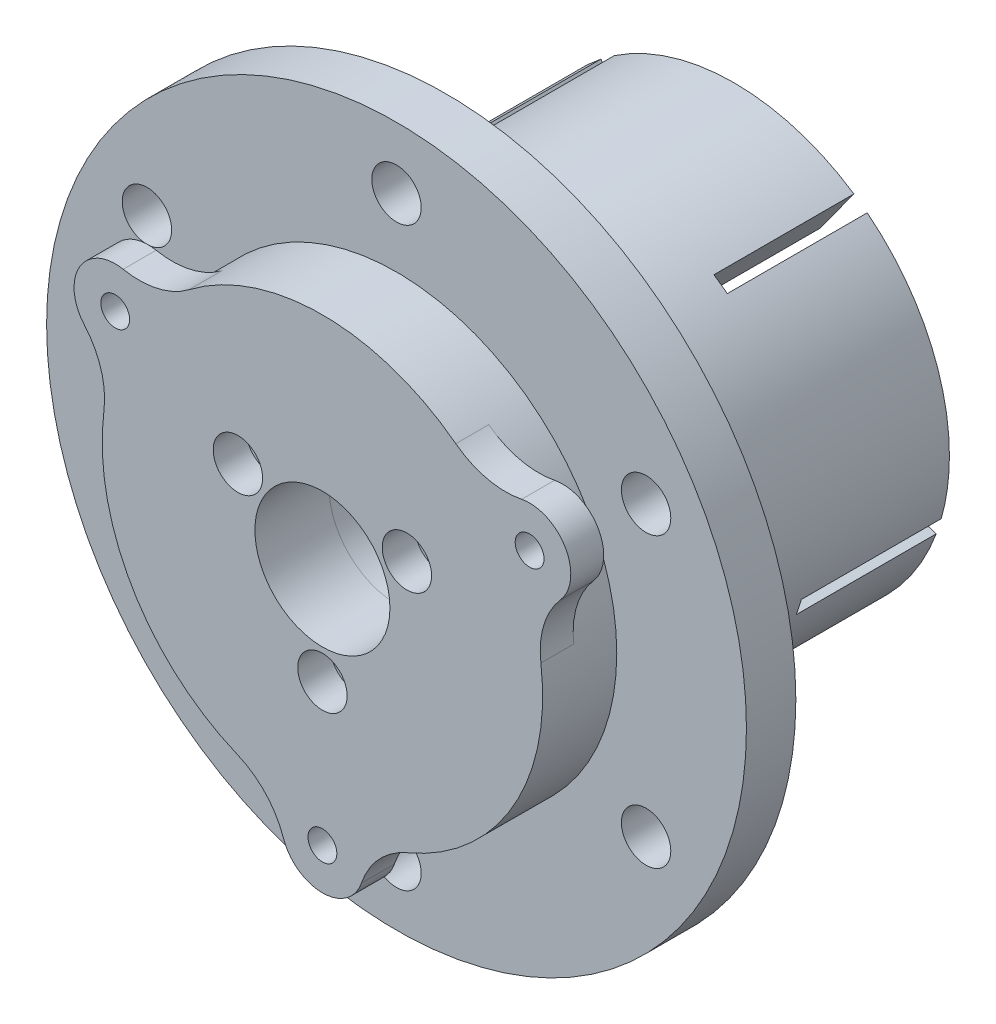
SolidWorks part; units mm, degrees
other "PCB Fixture"
other "Fanatec adapter V2"
ref_plane "Front Plane" through (0, 0, 0) normal (0, 0, 1) x (1, 0, 0)
ref_plane "Top Plane" through (0, 0, 0) normal (0, 1, 0) x (1, 0, 0)
ref_plane "Right Plane" through (0, 0, 0) normal (1, 0, 0) x (0, 0, -1)
sketch "Sketch1" plane through (0, 0, 0) normal (0, 0, 1) x (1, 0, 0)
  line L1 (-2.9, 18.9291) -> (2.9, 18.9291) construction
  line L2 (-2.9, 18.9291) -> (-2.9, 16.7508)
  line L4 (2.9, 18.9291) -> (2.9, 16.7508)
  circle A0 centre (0, 0) radius 19.15
  circle A1 centre (0, 0) radius 17
  circle A2 centre (0, 0) radius 26.15
  point P7 (0, 17)
  point P13 (0, 18.9291)
  dimension "D1" = 38.3
  dimension "D3" = 34
  dimension "D4" = 7
  dimension "D2" = 5.8
extrude "Boss-Extrude1" add sketch "Sketch1" against normal blind 35 contours A2 A0 | L1 L2 A1 L4 | A0 L1 region at (0, 19.0175, 0) region at (0, 17.9218, 0) region at (-25.4104, 0, 0)
fillet "Fillet1" radius 0.7 2 edges at (2.9, 18.9291, -17.5) (-2.9, 18.9291, -17.5)
sketch "Sketch2" plane through (0, 0, 0) normal (0, 0, 1) x (1, 0, 0)
  line L0 (0, -8.2) -> (0, -15.5) construction
  circle A0 centre (0, 35) radius 3
  circle A1 centre (30.3109, 17.5) radius 3
  circle A2 centre (30.3109, -17.5) radius 3
  circle A3 centre (0, -35) radius 3
  circle A4 centre (-30.3109, -17.5) radius 3
  circle A5 centre (-30.3109, 17.5) radius 3
  circle A6 centre (0, 0) radius 42.5
  circle A7 centre (0, 0) radius 8.2
  circle A8 centre (0, 0) radius 17 construction
  circle A10 centre (0, 0) radius 17
  circle A11 centre (0, -11.85) radius 1.35
  circle A13 centre (-10.2624, 5.925) radius 1.35
  circle A14 centre (10.2624, 5.925) radius 1.35
  point P15 (0, 0)
  point P34 (0, 0)
  dimension "D2" = 6
  dimension "D4" = 85
  dimension "D5" = 16.4
  dimension "D6" = 2.7
  dimension "D1" = 35
  dimension "D9" = 15.5
  dimension "D3" = 6
  dimension "D7" = 3
extrude "Boss-Extrude2" add sketch "Sketch2" along normal blind 6 contours A6 A10 A0 A1 A2 A3 A4 A5 | A10 A7 region at (-41.2979, 0, 0) region at (-16.5192, 0, 0)
sketch "Sketch3" plane through (0, 0, -35) normal (0, 0, -1) x (-1, 0, 0)
  line L1 (-1, -27.5229) -> (1, -27.5229)
  line L2 (0, 0) -> (0, -27.5229) construction
  line L3 (-1, -27.5229) -> (-1, 0)
  line L4 (-1, 0) -> (1, 0)
  line L5 (1, -27.5229) -> (1, 0)
  dimension "D1" = 2
extrude "Cut-Extrude1" cut sketch "Sketch3" against normal blind 17
pattern_circular "CirPattern1" count 5 over 360 about axis through (0, 0, -35) along (0, 0, 1) of "Cut-Extrude1"
chamfer "Chamfer1" distance 8 angle 45 1 edges at (26.15, 0, 0)
sketch "Sketch4" plane through (0, 0, 0) normal (0, 0, -1) x (-1, 0, 0)
  circle A0 centre (0, 35) radius 8
  circle A1 centre (30.3109, 17.5) radius 8
  circle A2 centre (30.3109, -17.5) radius 8
  circle A3 centre (0, -35) radius 8
  circle A4 centre (-30.3109, -17.5) radius 8
  circle A5 centre (-30.3109, 17.5) radius 8
  point P15 (0, 0)
  dimension "D1" = 16
  dimension "D2" = 6
extrude "Cut-Extrude2" cut sketch "Sketch4" along normal through all
sketch "Sketch6" plane through (0, 0, 6) normal (0, 0, 1) x (1, 0, 0)
  circle A0 centre (-10.2624, 5.925) radius 4
  dimension "D1" = 8
sketch "Sketch7" plane through (0, 0, 6) normal (0, 0, 1) x (1, 0, 0)
  circle A0 centre (-10.2624, 5.925) radius 2.4
  circle A1 centre (10.2624, 5.925) radius 2.4
  circle A2 centre (0, -11.85) radius 2.4
  dimension "D1" = 4.8
extrude "Cut-Extrude3" cut sketch "Sketch7" against normal offset from surface (3 mm away) 3 up to face at (1.35, -11.85, 0)
chamfer "Chamfer2" distance 1.1 angle 40 3 edges at (-7.8624, 5.925, 3) (2.4, -11.85, 3) (12.6624, 5.925, 3) first distance on face at (-8.9124, 5.925, 3) first distance on face at (1.35, -11.85, 3) first distance on face at (11.6124, 5.925, 3)
sketch "Sketch8" [suppressed] plane through (0, 0, 0) normal (1, 0, 0) x (0, 0, -1)
  line L1 (18, 56.9437) -> (0, 56.9437)
  line L2 (18, 56.9437) -> (18, -56.9437)
  line L3 (18, -56.9437) -> (0, -56.9437)
  line L4 (0, 56.9437) -> (0, -56.9437)
extrude "3d print test Cut-Extrude5" [suppressed] cut sketch "Sketch8" against normal through all both and the other way through all flip side to cut
sketch "Sketch9" plane through (0, 0, 6) normal (0, 0, 1) x (1, 0, 0)
  line L0 (-25.165, 14.529) -> (25.165, 14.529) construction
  line L1 (25.165, 14.529) -> (0, -29.058) construction
  line L2 (0, -29.058) -> (-25.165, 14.529) construction
  line L3 (0, 0) -> (25.165, 14.529) construction
  circle A2 centre (-10.2624, 5.925) radius 1.75
  circle A3 centre (10.2624, 5.925) radius 1.75
  circle A4 centre (0, -11.85) radius 1.75
  circle A5 centre (0, 0) radius 7.75
  circle A7 centre (0, 0) radius 26.75
  circle A8 centre (-25.165, 14.529) radius 1.75
  circle A9 centre (25.165, 14.529) radius 1.75
  circle A10 centre (0, -29.058) radius 1.75
  arc A11 (-20.7519, 16.8795) -> (-24.9941, 9.5319) centre (-25.165, 14.529) ccw
  arc A12 (24.9941, 9.5319) -> (20.7519, 16.8795) centre (25.165, 14.529) ccw
  arc A13 (-4.2421, -26.4115) -> (4.2421, -26.4115) centre (0, -29.058) ccw
  circle M5 centre (-10.2624, 5.925) radius 2.4
  circle M6 centre (10.2624, 5.925) radius 2.4
  circle M7 centre (0, -11.85) radius 2.4
  circle M9 centre (30.3109, 17.5) radius 3
  circle M11 centre (0, -35) radius 3
  circle M13 centre (-30.3109, 17.5) radius 3
  circle M15 centre (0, 0) radius 8.2
  dimension "D1" = 3.5
  dimension "D2" = 15.5
  dimension "D3" = 53.5
  dimension "D5" = 3.5
  dimension "D6" = 10
  dimension "D4" = 50.33
extrude "Boss-Extrude3" add sketch "Sketch9" along normal blind 9 separate body contours A7 M5 M7 M15 M6 | A2 M5 | A3 M6 | A4 M7 region at (19.7839, -16.8598, 6) region at (-12.5945, 5.925, 6) region at (7.9303, 5.925, 6) region at (-2.3321, -11.85, 6)
shell "Shell1" thickness 4 removed face at (8.2, 0, 6)
extrude "Boss-Extrude4" add sketch "Sketch9<3>" against normal blind 4 from surface contours A7 A11 A8 M13 | A11 M13 | A12 M9 | A12 A7 A9 M9 | A7 A13 A10 M11 | A13 M11 region at (23.2851, 13.4437, 6) region at (4.7358, -30.2278, 6) region at (28.6506, 16.5415, 6) region at (0, -33.0829, 6) region at (-23.2851, 13.4437, 6) region at (-28.6506, 16.5415, 6) starting at face at (8.2, 0, 15)
sketch "Sketch9<3>" plane through (0, 0, 6) normal (0, 0, 1) x (1, 0, 0) same geometry as "Sketch9"
fillet "Fillet2" radius 10 6 edges at (-20.7519, 16.8795, 13) (20.7519, 16.8795, 13) (24.9941, 9.5319, 13) (4.2421, -26.4115, 13) (-4.2421, -26.4115, 13) (-24.9941, 9.5319, 13)
sketch "Sketch10" plane through (0, 0, 15) normal (0, 0, 1) x (1, 0, 0)
  circle A0 centre (-10.2624, 5.925) radius 3
  circle A1 centre (10.2624, 5.925) radius 3
  circle A2 centre (0, -11.85) radius 3
  dimension "D1" = 6
extrude "Cut-Extrude4" cut sketch "Sketch10" against normal blind 4
